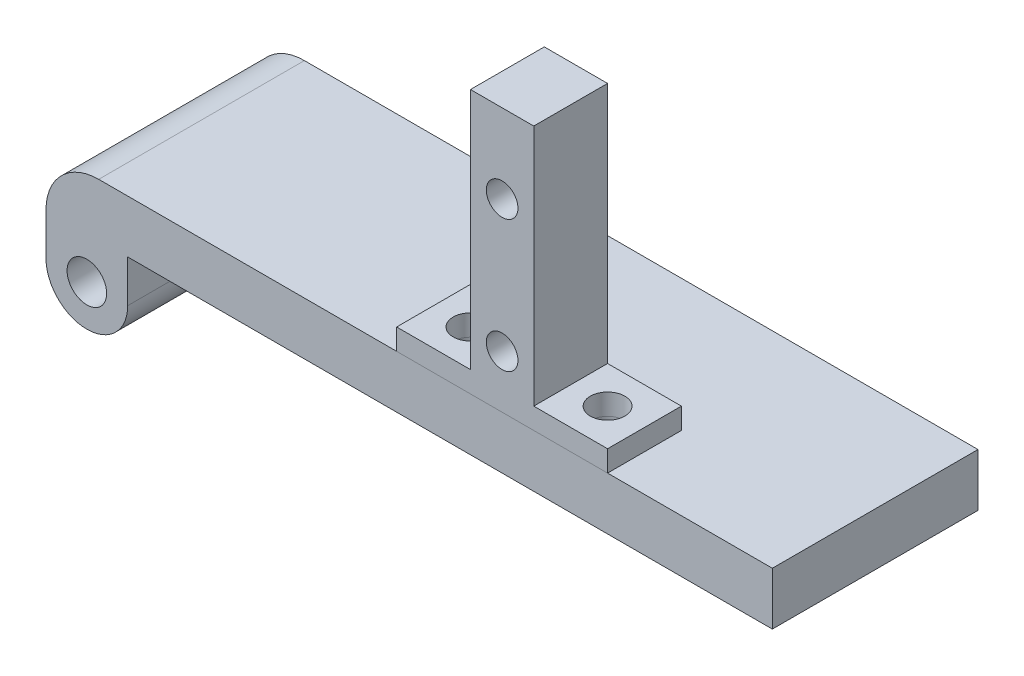
SolidWorks part; units mm, degrees
other "Lever Arm"
other "Motor Mount"
ref_plane "Front Plane" through (0, 0, 0) normal (0, 0, 1) x (1, 0, 0)
ref_plane "Top Plane" through (0, 0, 0) normal (0, 1, 0) x (1, 0, 0)
ref_plane "Right Plane" through (0, 0, 0) normal (1, 0, 0) x (0, 0, -1)
sketch "Sketch1" plane through (0, 0, 0) normal (0, 0, 1) x (1, 0, 0)
  line L0 (-37.3856, -8.255) -> (-37.3856, -3.175)
  line L1 (-37.3856, 3.175) -> (37.3856, 3.175)
  line L2 (-37.3856, 3.175) -> (-37.3856, -3.175)
  line L3 (-27.5431, -3.175) -> (37.3856, -3.175)
  line L4 (37.3856, 3.175) -> (37.3856, -3.175)
  line L5 (-37.3856, 3.175) -> (37.3856, -3.175) construction
  line L6 (-37.3856, -3.175) -> (37.3856, 3.175) construction
  line L7 (-27.5431, -8.255) -> (-27.5431, -3.175)
  circle A0 centre (-32.4644, -8.255) radius 2.3812
  arc A1 (-37.3856, -8.255) -> (-27.5431, -8.255) centre (-32.4644, -8.255) ccw
  point P0 (0, 0)
  dimension "D1" = 4.7625
  dimension "D3" = 2.54
  dimension "D2" = 6.35
  dimension "D4" = 69.85
  dimension "D5" = 5.08
extrude "Boss-Extrude1" add sketch "Sketch1" along normal blind 38.1
fillet "Fillet1" radius 6.35 1 edges at (-37.3856, 3.175, 19.05)
sketch "Sketch3" plane through (37.3856, 0, 0) normal (1, 0, 0) x (0, 0, -1)
  line L4 (0, -3.175) -> (0, 3.175)
  line L5 (0, 3.175) -> (-38.1, 3.175)
  line L6 (-38.1, 3.175) -> (-38.1, -3.175)
  line L7 (-38.1, -3.175) -> (0, -3.175)
  line L8 (0, -3.175) -> (0, 3.175)
  line L9 (0, 3.175) -> (-38.1, 3.175)
  line L10 (-38.1, 3.175) -> (-38.1, -3.175)
  line L11 (-38.1, -3.175) -> (0, -3.175)
  dimension "D1" = 0
extrude "Boss-Extrude2" add sketch "Sketch3" along normal blind 12.7
sketch "Sketch2" plane through (0, 3.175, 0) normal (0, 1, 0) x (1, 0, 0)
  line L1 (48.4981, -15.875) -> (11.9856, -15.875) construction
  line L2 (48.4981, -15.875) -> (48.4981, 0) construction
  line L3 (48.4981, 0) -> (11.9856, 0) construction
  line L4 (11.9856, -15.875) -> (11.9856, 0) construction
  line L5 (48.4981, -15.875) -> (11.9856, 0) construction
  line L6 (48.4981, 0) -> (11.9856, -15.875) construction
  line L7 (11.9856, -17.4625) -> (-16.5894, -17.4625) construction
  line L8 (11.9856, -17.4625) -> (11.9856, 1.5875) construction
  line L9 (11.9856, 1.5875) -> (-16.5894, 1.5875) construction
  line L10 (-16.5894, -17.4625) -> (-16.5894, 1.5875) construction
  line L11 (11.9856, -17.4625) -> (-16.5894, 1.5875) construction
  line L12 (11.9856, 1.5875) -> (-16.5894, -17.4625) construction
  line L13 (37.3856, -25.4) -> (37.3856, 9.525) construction
  line L14 (50.0856, 0) -> (-31.0356, 0) construction
  line L15 (-34.8456, -38.1) -> (-30.0831, -38.1) construction
  line L16 (-34.8456, -38.1) -> (-30.0831, -38.1) construction
  line L18 (21.3519, -24.765) -> (13.7319, -24.765)
  line L19 (21.3519, -24.765) -> (21.3519, -15.875)
  line L20 (21.3519, -15.875) -> (13.7319, -15.875)
  line L21 (13.7319, -24.765) -> (13.7319, -15.875)
  line L22 (21.3519, -24.765) -> (13.7319, -15.875) construction
  line L23 (21.3519, -15.875) -> (13.7319, -24.765) construction
  point P0 (30.2419, -7.9375)
  point P5 (17.5419, -20.32)
  point P6 (-2.3019, -7.9375)
  point P15 (17.5419, -20.32)
  point P21 (-32.4644, -38.1)
  point P26 (37.3856, -7.9375)
  dimension "Motor_Pos" = 15.875
  dimension "D2" = 36.5125
  dimension "D3" = 28.575
  dimension "D4" = 19.05
  dimension "D5" = 5.5562
  dimension "D6" = 11.1125
  dimension "D7" = 34.925
  dimension "D8" = 69.85
  dimension "D9" = 8.89
  dimension "D10" = 7.62
extrude "Boss-Extrude3" add sketch "Sketch2" along normal blind 31.75
sketch "Sketch5" plane through (0, 0, 24.765) normal (0, 0, 1) x (1, 0, 0)
  line L0 (17.5419, 34.925) -> (17.5419, 3.175) construction
  line L1 (13.7319, 34.925) -> (21.3519, 34.925) construction
  line L2 (13.7319, 3.175) -> (21.3519, 3.175) construction
  circle A0 centre (17.5419, 9.525) radius 1.905
  circle A1 centre (17.5419, 25.4) radius 1.905
  dimension "D1" = 3.81
  dimension "D2" = 15.875
  dimension "D3" = 6.35
extrude "Cut-Extrude1" cut sketch "Sketch5" against normal through all both and the other way through all
sketch "Sketch6" plane through (0, 3.175, 0) normal (0, 1, 0) x (1, 0, 0)
  line L0 (13.7319, -24.765) -> (21.3519, -24.765) construction
  line L1 (30.2419, -24.765) -> (4.8419, -24.765)
  line L2 (30.2419, -24.765) -> (30.2419, -15.875)
  line L3 (30.2419, -15.875) -> (4.8419, -15.875)
  line L4 (4.8419, -24.765) -> (4.8419, -15.875)
  line L5 (30.2419, -24.765) -> (4.8419, -15.875) construction
  line L6 (30.2419, -15.875) -> (4.8419, -24.765) construction
  line L7 (21.3519, -15.875) -> (13.7319, -15.875) construction
  line L8 (15.6369, -24.765) -> (19.4469, -24.765) construction
  line L9 (15.6369, -24.765) -> (19.4469, -24.765) construction
  line L10 (13.7319, -15.875) -> (13.7319, -24.765) construction
  point P0 (17.5419, -20.32)
  point P14 (17.5419, -24.765)
  dimension "D1" = 25.4
  dimension "D2" = 8.89
  dimension "D3" = 8.89
extrude "Boss-Extrude4" add sketch "Sketch6" along normal blind 2.54
sketch "Sketch7" plane through (0, 5.715, 0) normal (0, 1, 0) x (1, 0, 0)
  line L0 (4.8419, -24.765) -> (30.2419, -24.765) construction
  line L1 (13.7319, -24.765) -> (4.8419, -24.765) construction
  line L2 (13.7319, -24.765) -> (13.7319, -15.875) construction
  line L3 (13.7319, -15.875) -> (4.8419, -15.875) construction
  line L4 (4.8419, -24.765) -> (4.8419, -15.875) construction
  line L5 (13.7319, -24.765) -> (4.8419, -15.875) construction
  line L6 (13.7319, -15.875) -> (4.8419, -24.765) construction
  line L7 (13.7319, -15.875) -> (13.7319, -24.765) construction
  line L8 (15.6369, -24.765) -> (19.4469, -24.765) construction
  line L9 (15.6369, -24.765) -> (19.4469, -24.765) construction
  line L10 (17.5419, -24.765) -> (17.5419, -15.875) construction
  line L11 (30.2419, -15.875) -> (4.8419, -15.875) construction
  circle A0 centre (9.2869, -20.32) radius 2.0828
  circle A2 centre (25.7969, -20.32) radius 2.0828
  point P14 (17.5419, -24.765)
  dimension "D1" = 4.1656
extrude "Cut-Extrude2" cut sketch "Sketch7" against normal through all both and the other way through all
ref_plane "Plane1" through (-27.5431, -3.175, 38.1) normal (1, 0, 0) x (0, 0, -1)
sketch "Sketch9" plane through (0, 0, 38.1) normal (0, 0, 1) x (1, 0, 0)
  line L0 (50.0856, 3.175) -> (50.0856, -3.175) construction
  line L1 (-27.5431, -3.175) -> (50.0856, -3.175) construction
  line L2 (-27.5431, -8.255) -> (-27.5431, -3.175) construction
  line L3 (-37.3856, -3.175) -> (-37.3856, -8.255) construction
  line L4 (50.0856, 3.175) -> (-31.0356, 3.175) construction
  line L5 (50.0856, 3.175) -> (50.0856, -3.175)
  line L6 (-27.5431, -3.175) -> (50.0856, -3.175)
  line L7 (-27.5431, -8.255) -> (-27.5431, -3.175)
  line L8 (-37.3856, -3.175) -> (-37.3856, -8.255)
  line L9 (50.0856, 3.175) -> (-31.0356, 3.175)
  arc A0 (-37.3856, -8.255) -> (-27.5431, -8.255) centre (-32.4644, -8.255) ccw construction
  arc A1 (-31.0356, 3.175) -> (-37.3856, -3.175) centre (-31.0356, -3.175) ccw construction
  arc A2 (-37.3856, -8.255) -> (-27.5431, -8.255) centre (-32.4644, -8.255) ccw
  arc A3 (-31.0356, 3.175) -> (-37.3856, -3.175) centre (-31.0356, -3.175) ccw
extrude "Cut-Extrude3" cut sketch "Sketch9" against normal up to surface (13.335 mm away) up to face at (15.6369, 9.525, 24.765)
split "Split1" bodies to split 111 resulting bodies 107 108 split by face at (13.5334, 3.175, 16.3513)
